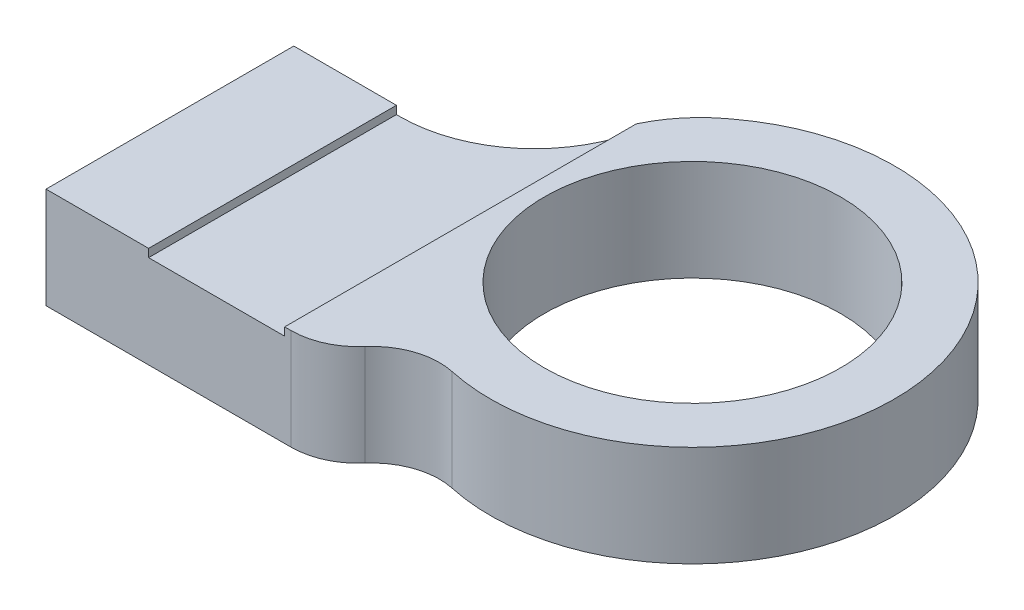
SolidWorks part; units mm, degrees
other "Markup1"
sketch "Sketch3" plane through (15, 2.5, 15) normal (0.0676, 0.9975, 0.0223) x (0.9945, -0.0692, 0.0785)
ref_plane "Front Plane" through (0, 0, 0) normal (0, 0, 1) x (1, 0, 0)
ref_plane "Top Plane" through (0, 0, 0) normal (0, 1, 0) x (1, 0, 0)
ref_plane "Right Plane" through (0, 0, 0) normal (1, 0, 0) x (0, 0, -1)
sketch "Sketch1" plane through (0, 0, 0) normal (0, 1, 0) x (1, 0, 0)
  line L1 (-30, -10) -> (-11.1803, -10)
  line L2 (-30, -10) -> (-30, 10)
  line L3 (-30, 10) -> (-11.1803, 10)
  arc A0 (-11.1803, -10) -> (-11.1803, 10) centre (0, 0) ccw
  point P3 (-20.5, 0)
  dimension "D3" = 20.5
  dimension "D4" = 10
  dimension "D5" = 30
extrude "Boss-Extrude1" add sketch "Sketch1" along normal blind 2.5
sketch "Sketch2" plane through (0, 2.5, 0) normal (0, 1, 0) x (1, 0, 0)
  line L0 (-30, -10) -> (-11.1803, -10) construction
  line L1 (-23.8803, -10) -> (-13.8803, -10)
  line L2 (-23.8803, -10) -> (-23.8803, 10)
  line L3 (-23.8803, 10) -> (-13.8803, 10)
  line L4 (-13.8803, -10) -> (-13.8803, 10)
  line L5 (-11.1803, 10) -> (-30, 10) construction
  dimension "D1" = 10
  dimension "D2" = 2.7
extrude "Cut-Extrude1" cut sketch "Sketch2" against normal blind 0.6
sketch "Sketch4" plane through (0, 2.5, 0) normal (0, 1, 0) x (1, 0, 0)
  circle A0 centre (0, 0) radius 11
extrude "Cut-Extrude2" cut sketch "Sketch4" against normal through all
sketch "Sketch6" plane through (0, 0, 0) normal (0, -1, 0) x (1, 0, 0)
  circle A0 centre (0, 0) radius 15
extrude "Boss-Extrude2" add sketch "Sketch6" along normal blind 5
sketch "Sketch7" plane through (0, 0, 0) normal (0, 1, 0) x (1, 0, 0)
  circle A0 centre (0, 0) radius 11
extrude "Cut-Extrude3" cut sketch "Sketch7" against normal through all
sketch "Sketch8" plane through (0, 0, 0) normal (0, -1, 0) x (1, 0, 0)
  line L1 (-30, 10) -> (-11.1803, 10)
  line L2 (-30, 10) -> (-30, -10)
  line L3 (-30, -10) -> (-11.1803, -10)
  line L4 (-11.1803, 10) -> (-11.1803, -10)
extrude "Boss-Extrude3" add sketch "Sketch8" along normal blind 5
fillet "Fillet1" radius 10 2 edges at (-11.1803, -1.25, -10) (-11.1803, -1.25, 10)
sketch "Sketch10" plane through (0, 0, 10) normal (0, 0, 1) x (1, 0, 0)
  line L0 (-30, -5) -> (-30, 2.5)
  line L1 (-30, 2.5) -> (-30, -5) construction
  line L2 (-30, 2.5) -> (-23.8803, 2.5) construction
  line L3 (-30, 2.5) -> (-23.8803, 2.5)
  line L4 (-23.8803, 2.5) -> (-23.8803, 1.9)
  line L5 (-23.8803, 1.9) -> (-13.8803, 1.9)
  line L6 (-13.8803, 1.9) -> (-13.8803, 2.5)
  line L7 (-13.8803, 2.5) -> (-9, 2.5)
  line L8 (-9, 2.5) -> (-9, -5)
  line L9 (-9, -5) -> (-30, -5)
extrude "Boss-Extrude4" add sketch "Sketch10" along normal blind 8
sketch "Sketch11" plane through (0, 0, 0) normal (0, 1, 0) x (1, 0, 0)
  line L6 (-30, 10) -> (-30, -18) construction
  line L7 (-30, 2) -> (-13.88, 2)
  line L8 (-30, 2) -> (-30, 12)
  line L9 (-30, 12) -> (-13.88, 12)
  line L10 (-13.88, 2) -> (-13.88, 12)
  line L11 (-23.8803, -18) -> (-30, -18) construction
  dimension "D1" = 10
  dimension "D2" = 20
  dimension "D3" = 16.12
extrude "Cut-Extrude6" cut sketch "Sketch11" against normal mid plane 20
fillet "Fillet2" radius 10 1 edges at (-13.88, -1.25, -10.0629)
fillet "Fillet3" radius 10 1 edges at (-13.88, -1.25, -2)
fillet "Fillet4" radius 5 1 edges at (-9, -1.25, 12)
fillet "Fillet5" radius 5 1 edges at (-9, -1.25, 18)
sketch "Sketch12" plane through (0, 2.5, 0) normal (0, 1, 0) x (1, 0, 0)
  line L1 (-13.8803, -18) -> (-12.2803, -18)
  line L2 (-13.8803, -18) -> (-13.8803, 14.0716)
  line L3 (-13.8803, 14.0716) -> (-12.2803, 14.0716)
  line L4 (-12.2803, -18) -> (-12.2803, 14.0716)
  dimension "D1" = 1.6
extrude "Cut-Extrude7" cut sketch "Sketch12" against normal blind 0.6
sketch "Sketch13" plane through (0, 1.9, 0) normal (0, 1, 0) x (1, 0, 0)
  line L0 (-12.2803, -18) -> (-23.8803, -18) construction
  line L1 (-23.8803, 2) -> (-22.3803, 2)
  line L2 (-23.8803, 2) -> (-23.8803, -18)
  line L3 (-23.8803, -18) -> (-22.3803, -18)
  line L4 (-22.3803, 2) -> (-22.3803, -18)
  dimension "D1" = 1.5
extrude "Boss-Extrude5" add sketch "Sketch13" along normal blind 0.6
sketch "Sketch14" plane through (0, 2.5, 0) normal (0, 1, 0) x (1, 0, 0)
  line L0 (-30, 2) -> (-30, -18) construction
  line L1 (-30, 0.4) -> (-12.2566, 0.4)
  line L2 (-30, 0.4) -> (-30, 17.0536)
  line L3 (-30, 17.0536) -> (-12.2566, 17.0536)
  line L4 (-12.2566, 0.4) -> (-12.2566, 17.0536)
  line L5 (-30, 2) -> (-22.3803, 2) construction
  dimension "D1" = 1.6
extrude "Cut-Extrude8" cut sketch "Sketch14" against normal through all
fillet "Fillet6" radius 10 1 edges at (-12.2566, -1.25, -0.4)
fillet "Fillet7" radius 10 1 edges at (-12.2566, -1.25, -8.8382)
